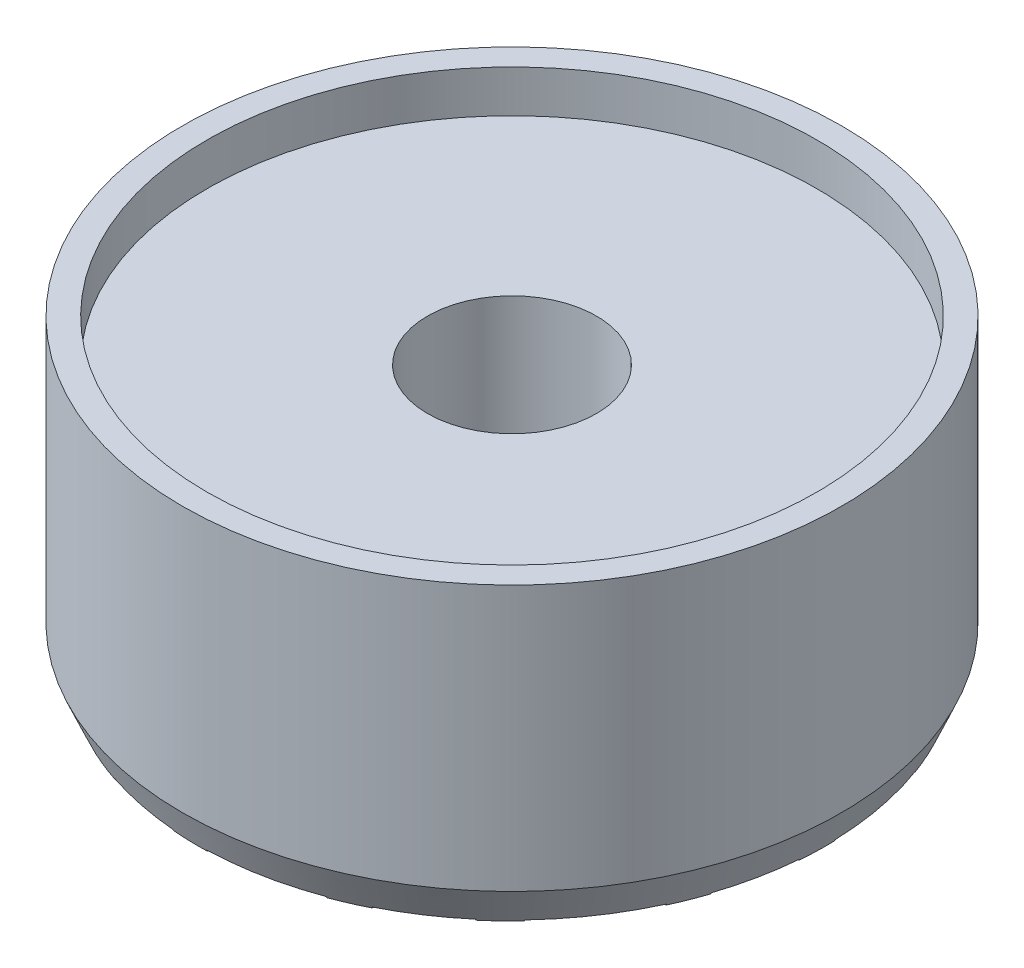
SolidWorks part; units mm, degrees
material "1060 Alloy"
ref_plane "Front Plane" through (0, 0, 0) normal (0, 0, 1) x (1, 0, 0)
ref_plane "Top Plane" through (0, 0, 0) normal (0, 1, 0) x (1, 0, 0)
ref_plane "Right Plane" through (0, 0, 0) normal (1, 0, 0) x (0, 0, -1)
sketch "Sketch1" plane through (0, 0, 0) normal (0, 1, 0) x (1, 0, 0)
  circle A0 centre (0, 0) radius 99.06
  dimension "D1" = 198.12
extrude "Boss-Extrude1" add sketch "Sketch1" along normal blind 88.9
sketch "Sketch2" plane through (0, 88.9, 0) normal (0, 1, 0) x (1, 0, 0)
  circle A0 centre (0, 0) radius 25.4
  dimension "D1" = 50.8
extrude "Cut-Extrude1" cut sketch "Sketch2" against normal blind 76.2
sketch "Sketch3" plane through (0, 88.9, 0) normal (0, 1, 0) x (1, 0, 0)
  circle A0 centre (0, 0) radius 91.6876
extrude "Cut-Extrude2" cut sketch "Sketch3" against normal blind 12.7
sketch "Sketch4" plane through (0, 0, 0) normal (0, 0, 1) x (1, 0, 0)
  line L0 (0, 0) -> (0, -39.6928)
  line L1 (0, -39.6928) -> (99.06, 0)
  line L2 (99.06, 0) -> (0, 0)
revolve "Revolve1" add sketch "Sketch4" angle 360 about L0
ref_plane "Plane1" through (0, -52.324, 0) normal (0, 1, 0) x (1, 0, 0)
sketch "Sketch5" plane through (0, -52.324, 0) normal (0, 1, 0) x (1, 0, 0)
  circle A0 centre (0, 0) radius 25.4
  dimension "D1" = 50.8
extrude "Cut-Extrude3" cut sketch "Sketch5" along normal blind 50.8
sketch "Sketch6" plane through (0, -52.324, 0) normal (0, 1, 0) x (1, 0, 0)
  line L0 (0, -25.4) -> (0, -99.06)
  line L1 (0, -99.06) -> (0, -25.4)
  line L2 (-34.0987, -93.0062) -> (-38.8334, -91.1309)
  line L3 (0, -99.06) -> (-5.08, -98.9297)
  line L4 (-24.8868, -58.42) -> (-38.8334, -91.1309)
  line L5 (-89.8768, -41.6539) -> (-21.1897, -14.0055)
  line L6 (-9.9547, -23.368) -> (-24.8868, -58.42)
  line L7 (-24.8868, -58.42) -> (-9.9547, -23.368)
  line L8 (-34.0987, -93.0062) -> (-5.08, -24.8868)
  line L9 (-5.08, -24.8868) -> (-5.08, -98.9297)
  line L10 (-58.9068, -23.7115) -> (-91.8987, -36.9799)
  line L11 (-23.5627, -9.4846) -> (-58.9068, -23.7115)
  line L12 (-17.9605, -17.9605) -> (-70.046, -70.046)
  line L13 (-21.1897, -14.0055) -> (-73.5459, -66.3617)
  line L14 (-89.8768, -41.6539) -> (-91.8987, -36.9799)
  line L15 (-70.046, -70.046) -> (-73.5459, -66.3617)
  line L16 (-93.0062, 34.0987) -> (-24.8868, 5.08)
  line L17 (-58.42, 24.8868) -> (-91.1309, 38.8334)
  line L18 (-23.368, 9.9547) -> (-58.42, 24.8868)
  line L19 (-25.4, 0) -> (-99.06, 0)
  line L20 (-24.8868, 5.08) -> (-98.9297, 5.08)
  line L21 (-93.0062, 34.0987) -> (-91.1309, 38.8334)
  line L22 (-99.06, 0) -> (-98.9297, 5.08)
  line L23 (-41.6539, 89.8768) -> (-14.0055, 21.1897)
  line L24 (-23.7115, 58.9068) -> (-36.9799, 91.8987)
  line L25 (-9.4846, 23.5627) -> (-23.7115, 58.9068)
  line L26 (-17.9605, 17.9605) -> (-70.046, 70.046)
  line L27 (-14.0055, 21.1897) -> (-66.3617, 73.5459)
  line L28 (-41.6539, 89.8768) -> (-36.9799, 91.8987)
  line L29 (-70.046, 70.046) -> (-66.3617, 73.5459)
  line L30 (34.0987, 93.0062) -> (5.08, 24.8868)
  line L31 (24.8868, 58.42) -> (38.8334, 91.1309)
  line L32 (9.9547, 23.368) -> (24.8868, 58.42)
  line L33 (0, 25.4) -> (0, 99.06)
  line L34 (5.08, 24.8868) -> (5.08, 98.9297)
  line L35 (34.0987, 93.0062) -> (38.8334, 91.1309)
  line L36 (0, 99.06) -> (5.08, 98.9297)
  line L37 (89.8768, 41.6539) -> (21.1897, 14.0055)
  line L38 (58.9068, 23.7115) -> (91.8987, 36.9799)
  line L39 (23.5627, 9.4846) -> (58.9068, 23.7115)
  line L40 (17.9605, 17.9605) -> (70.046, 70.046)
  line L41 (21.1897, 14.0055) -> (73.5459, 66.3617)
  line L42 (89.8768, 41.6539) -> (91.8987, 36.9799)
  line L43 (70.046, 70.046) -> (73.5459, 66.3617)
  line L44 (93.0062, -34.0987) -> (24.8868, -5.08)
  line L45 (58.42, -24.8868) -> (91.1309, -38.8334)
  line L46 (23.368, -9.9547) -> (58.42, -24.8868)
  line L47 (25.4, 0) -> (99.06, 0)
  line L48 (24.8868, -5.08) -> (98.9297, -5.08)
  line L49 (93.0062, -34.0987) -> (91.1309, -38.8334)
  line L50 (99.06, 0) -> (98.9297, -5.08)
  line L51 (41.6539, -89.8768) -> (14.0055, -21.1897)
  line L52 (23.7115, -58.9068) -> (36.9799, -91.8987)
  line L53 (9.4846, -23.5627) -> (23.7115, -58.9068)
  line L54 (17.9605, -17.9605) -> (70.046, -70.046)
  line L55 (14.0055, -21.1897) -> (66.3617, -73.5459)
  line L56 (41.6539, -89.8768) -> (36.9799, -91.8987)
  line L57 (70.046, -70.046) -> (66.3617, -73.5459)
  arc A0 (-9.9547, -23.368) -> (0, -25.4) centre (0, 0) ccw
  circle A1 centre (0, 0) radius 99.06 construction
  circle A2 centre (0, 0) radius 99.06
  circle A3 centre (0, 0) radius 25.4 construction
  arc A4 (-23.5627, -9.4846) -> (-17.9605, -17.9605) centre (0, 0) ccw
  arc A5 (-23.368, 9.9547) -> (-25.4, 0) centre (0, 0) ccw
  arc A6 (-9.4846, 23.5627) -> (-17.9605, 17.9605) centre (0, 0) ccw
  arc A7 (9.9547, 23.368) -> (0, 25.4) centre (0, 0) ccw
  arc A8 (23.5627, 9.4846) -> (17.9605, 17.9605) centre (0, 0) ccw
  arc A9 (23.368, -9.9547) -> (25.4, 0) centre (0, 0) ccw
  arc A10 (9.4846, -23.5627) -> (17.9605, -17.9605) centre (0, 0) ccw
  point P74 (0, 0)
  dimension "D1" = 8
  dimension "D2" = 5.08
  dimension "D3" = 5.08
extrude "Cut-Extrude4" cut sketch "Sketch6" along normal blind 50.8 draft 3 contours L8 A2 L9 | L53 A10 L54 A2 L45 L46 A9 L47 L38 L39 A8 L40 L31 L32 A7 L33 L24 L25 A6 L26 L17 L18 A5 L19 L10 L11 A4 L12 L4 L6 A0 L0 L52 | L51 A2 L55 | L44 A2 L48 | L37 A2 L41 | L30 A2 L34 | L23 A2 L27 | L16 A2 L20 | L5 A2 L13 region at (0, -52.324, 0) region at (-14.8518, -52.324, 72.7585) region at (40.9463, -52.324, 61.9498) region at (-61.9498, -52.324, 40.9463) region at (72.7585, -52.324, 14.8518) region at (-72.7585, -52.324, -14.8518) region at (61.9498, -52.324, -40.9463) region at (-40.9463, -52.324, -61.9498) region at (14.8518, -52.324, -72.7585)
sketch "Sketch8" plane through (0, 0, 0) normal (0, 1, 0) x (1, 0, 0)
  circle A0 centre (0, 0) radius 25.4
extrude "Boss-Extrude2" add sketch "Sketch8" against normal blind 30.48
sketch "Sketch9" plane through (0, 0, 0) normal (0, 1, 0) x (1, 0, 0)
  circle A0 centre (0, 0) radius 22.86
  dimension "D1" = 45.72
extrude "Cut-Extrude5" cut sketch "Sketch9" against normal blind 30.48
chamfer "Chamfer1" distance 5.08 angle 45 1 edges at (0, 0, 99.06) first distance on face at (-65.4848, -7.4299, 46.4641)
